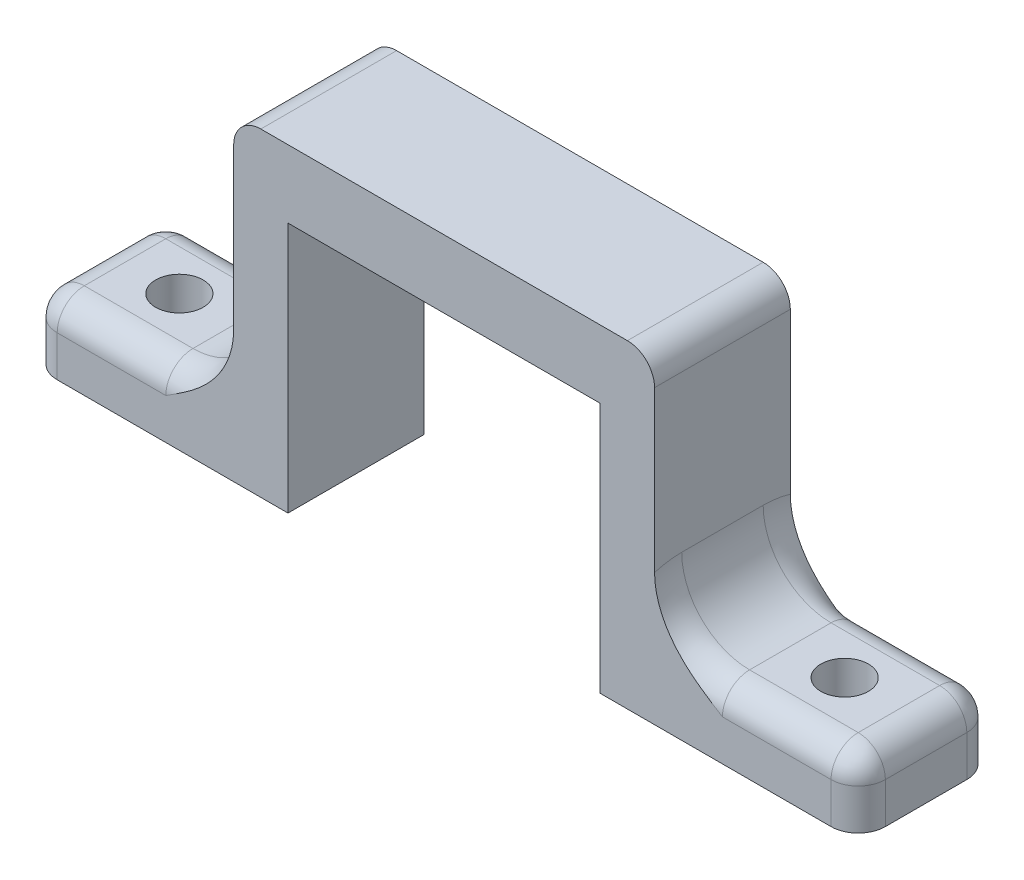
SolidWorks part; units mm, degrees
ref_plane "Front Plane" through (0, 0, 0) normal (0, 0, 1) x (1, 0, 0)
ref_plane "Top Plane" through (0, 0, 0) normal (0, 1, 0) x (1, 0, 0)
ref_plane "Right Plane" through (0, 0, 0) normal (1, 0, 0) x (0, 0, -1)
sketch "Sketch1" plane through (0, 0, 0) normal (0, 1, 0) x (1, 0, 0)
  line L1 (0, 0) -> (-23, 0)
  line L2 (0, 0) -> (0, -10)
  line L3 (0, -10) -> (-23, -10)
  line L4 (-23, 0) -> (-23, -10)
  line L5 (0, 0) -> (4, 0)
  line L6 (0, 0) -> (0, -10)
  line L7 (0, -10) -> (4, -10)
  line L8 (4, 0) -> (4, -10)
  line L9 (-23, 0) -> (-27, 0)
  line L10 (-23, 0) -> (-23, -10)
  line L11 (-23, -10) -> (-27, -10)
  line L12 (-27, 0) -> (-27, -10)
  line L13 (4, 0) -> (19, 0)
  line L14 (4, 0) -> (4, -10)
  line L15 (4, -10) -> (19, -10)
  line L16 (19, 0) -> (19, -10)
  line L17 (-27, 0) -> (-42, 0)
  line L18 (-27, 0) -> (-27, -10)
  line L19 (-27, -10) -> (-42, -10)
  line L20 (-42, 0) -> (-42, -10)
  dimension "D1" = 23
  dimension "D2" = 10
  dimension "D3" = 4
  dimension "D4" = 15
extrude "Boss-Extrude1" add sketch "Sketch1" along normal blind 23.5 contours L17 L20 L19 L12 | L9 L12 L11 L4 | L1 L4 L3 L2 | L8 L5 L2 L7 | L16 L13 L8 L15 region at (-11.5, 0, 5) region at (2, 0, 5) region at (-25, 0, 5) region at (11.5, 0, 5) region at (-34.5, 0, 5)
extrude "Cut-Extrude1" cut sketch "Sketch1<3>" along normal blind 18.5 contours L1 L4 L3 L2 region at (-11.5, 0, 5)
sketch "Sketch1<3>" plane through (0, 0, 0) normal (0, 1, 0) x (1, 0, 0) same geometry as "Sketch1"
extrude "Cut-Extrude2" cut sketch "Sketch1<4>" against normal offset from surface (18.5 mm away) 5 from surface contours L17 L20 L19 L12 | L16 L13 L8 L15 region at (11.5, 0, 5) region at (-34.5, 0, 5) up to face at (9.5, 0, 5) starting at face at (-11.5, 23.5, 5)
sketch "Sketch1<4>" plane through (0, 0, 0) normal (0, 1, 0) x (1, 0, 0) same geometry as "Sketch1"
fillet "Fillet1" radius 2 6 edges at (19, 2.5, 0) (19, 2.5, 10) (-42, 2.5, 0) (-42, 2.5, 10) (4, 23.5, 5) (-27, 23.5, 5)
fillet "Fillet2" radius 2 10 edges at (-33.5, 5, 10) (-41.4142, 5, 9.4142) (-42, 5, 5) (-41.4142, 5, 0.5858) (10.5, 5, 10) (18.4142, 5, 9.4142) (19, 5, 5) (18.4142, 5, 0.5858) (-33.5, 5, 0) (10.5, 5, 0)
fillet "Fillet3" radius 5 6 edges at (-27, 4.4142, 0.5858) (-27, 4.4142, 9.4142) (4, 4.4142, 0.5858) (4, 4.4142, 9.4142) (-27, 5, 5) (4, 5, 5)
sketch "Sketch2" plane through (0, 5, 0) normal (0, 1, 0) x (1, 0, 0)
  line L0 (9, -8) -> (17, -8) construction
  line L2 (17, -8) -> (17, -2) construction
  line L3 (-40, -2) -> (-40, -8) construction
  circle A0 centre (13, -5) radius 1.75
  circle A1 centre (-36, -5) radius 1.75
  point P4 (0, 0)
  point P5 (0, 0)
  dimension "D1" = 3.5
  dimension "D2" = 3
  dimension "D3" = 4
  dimension "D4" = 4
extrude "Cut-Extrude3" cut sketch "Sketch2" against normal up to next
